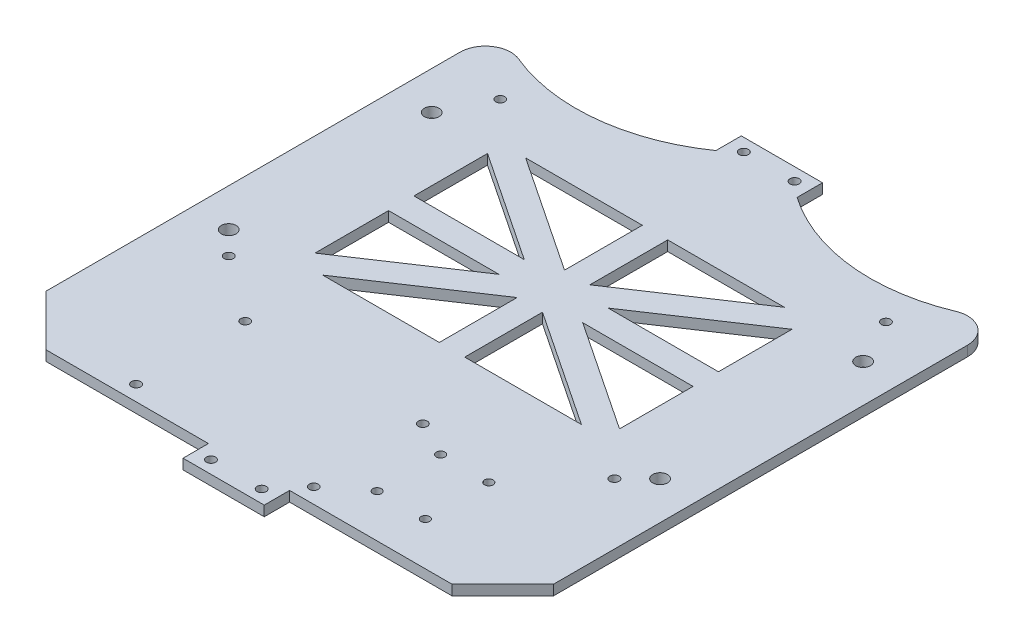
SolidWorks part; units mm, degrees
material "PLA"
ref_plane "Front Plane" through (0, 0, 0) normal (0, 0, 1) x (1, 0, 0)
ref_plane "Top Plane" through (0, 0, 0) normal (0, 1, 0) x (1, 0, 0)
ref_plane "Right Plane" through (0, 0, 0) normal (1, 0, 0) x (0, 0, -1)
sketch "Sketch1" plane through (0, 0, 0) normal (0, 1, 0) x (1, 0, 0)
  line L0 (-100, -229.5) -> (100, -229.5)
  line L1 (100, -229.5) -> (100, -29.5)
  line L2 (100, -29.5) -> (16, -29.5) construction
  line L3 (16, -29.5) -> (16, -19.5)
  line L10 (-16, -29.5) -> (-100, -29.5) construction
  line L11 (-100, -29.5) -> (-100, -229.5)
  line L12 (0, -222) -> (0, 5.5) construction
  line L17 (-10, -24.5) -> (10, -24.5) construction
  line L18 (-16, -29.5) -> (16, -29.5) construction
  line L19 (-10, -234.5) -> (10, -234.5) construction
  line L20 (-16.5139, -104.5) -> (-60, -104.5)
  line L21 (-60, -114.5) -> (-16.5139, -114.5)
  line L22 (-5, -118.8426) -> (-5, -149.5)
  line L27 (5, -118.8426) -> (5, -149.5)
  line L28 (60, -109.5) -> (-60, -109.5) construction
  line L29 (60, -114.5) -> (16.5139, -114.5)
  line L30 (16.5139, -104.5) -> (60, -104.5)
  line L31 (5, -100.1574) -> (5, -69.5)
  line L32 (-5, -100.1574) -> (-5, -69.5)
  line L54 (-60, -69.5) -> (-60, -149.5)
  line L55 (-60, -149.5) -> (60, -149.5)
  line L56 (60, -149.5) -> (60, -69.5)
  line L57 (60, -69.5) -> (-60, -69.5)
  line L59 (-16, -19.5) -> (16, -19.5)
  line L61 (-16, -229.5) -> (-16, -239.5)
  line L62 (-16, -239.5) -> (16, -239.5)
  line L63 (16, -239.5) -> (16, -229.5)
  line L64 (17, -190.5) -> (17, -217.5)
  line L65 (17, -217.5) -> (-18, -217.5)
  line L66 (-18, -217.5) -> (-18, -190.5)
  line L67 (-18, -190.5) -> (17, -190.5)
  line L68 (-50.5, -223.5) -> (-50.5, -180.5) construction
  line L69 (-50.5, -180.5) -> (19.5, -180.5) construction
  line L70 (19.5, -180.5) -> (19.5, -223.5) construction
  line L74 (-60, -75.5093) -> (50.9861, -149.5)
  line L75 (60, -143.4907) -> (-50.9861, -69.5)
  line L76 (-60, -143.4907) -> (50.9861, -69.5)
  line L77 (-50.9861, -149.5) -> (60, -75.5093)
  line L78 (60, -69.5) -> (-60, -149.5) construction
  line L79 (-60, -69.5) -> (60, -149.5) construction
  line L81 (-16, -19.5) -> (-16, -29.5)
  arc A11 (16, -29.5) -> (100, -29.5) centre (58, 30.5) ccw
  arc A12 (-16, -29.5) -> (-100, -29.5) centre (-58, 30.5) cw
  point P5 (-76, -161.5)
  point P6 (-76, -54.5)
  point P7 (76, -161.5)
  point P8 (76, -54.5)
  point P10 (-10, -24.5)
  point P11 (10, -24.5)
  point P12 (0, -229.5)
  point P27 (0, -109.5)
  point P37 (0, -109.5)
  point P53 (0, -239.5)
  point P58 (-50.5, -180.5)
  point P59 (-50.5, -223.5)
  point P60 (19.5, -180.5)
  point P62 (19.5, -223.5)
  point P131 (-85, -72.5)
  point P132 (-85, -152.5)
  point P133 (85, -152.5)
  point P134 (85, -72.5)
  dimension "D29" = 22
  dimension "D30" = 10
  dimension "D31" = 27
  dimension "D39" = 10
  dimension "D12" = 152
  dimension "D13" = 60
  dimension "D4" = 200
  dimension "D8" = 30.5
  dimension "D9" = 200
  dimension "D10" = 10
  dimension "D11" = 16
  dimension "D14" = 107
  dimension "D15" = 25
  dimension "D16" = 20
  dimension "D17" = 5
  dimension "D18" = 20
  dimension "D19" = 40
  dimension "D20" = 10
  dimension "D21" = 10
  dimension "D22" = 19.5
  dimension "D32" = 35
  dimension "D33" = 17
  dimension "D37" = 43
  dimension "D38" = 70
  dimension "D58" = 120
  dimension "D60" = 80
  dimension "D67" = 80
  dimension "D68" = 170
  dimension "D69" = 77
  dimension "D75" = 10
  dimension "D76" = 10
extrude "Boss-Extrude1" add sketch "Sketch1" along normal blind 4 contours L12 | L12 | A12 L11 L0 L1 A11 L3 L57 L56 L55 L54 | L74 L76 L75 L57 L54 | L74 L77 L75 L76 | L77 L74 L55 L56 L75 | L55 L77 L74 L76 L54 | L75 L77 L56 L57 L76 | L62 L63 L0 L61 | L21 L76 L74 L20 L54 | L75 L76 L31 L57 L32 | L77 L75 L29 L56 L30 | L77 L22 L55 L27 L74 | L67 L66 L65 L64 region at (-97.1, 0, 129.5) region at (0, 0, 234.5) region at (-36.3323, 0, 109.5) region at (-31.1426, 0, 88.7382) region at (0, 0, 109.5) region at (-31.1426, 0, 130.2618) region at (31.1426, 0, 130.2618) region at (0, 0, 133.3236) region at (31.1426, 0, 88.7382) region at (0, 0, 85.6764) region at (36.3323, 0, 109.5) region at (-0.5, 0, 204)
hole_wizard "M5 Clearance Hole1" positions "Sketch15" profile "Sketch14" hole size "M5" standard "ISO" end condition through all
sketch "Sketch15" plane through (0, 4, 0) normal (0, 1, 0) x (1, 0, 0)
  point P0 (-85, -72.5)
  point P3 (-85, -152.5)
  point P6 (85, -152.5)
  point P9 (85, -72.5)
sketch "Sketch14" plane through (-85, 4, 72.5) normal (1, 0, 0) x (0, 0, 1)
  line L0 (0, 0) -> (0, 4)
  line L1 (0, 4) -> (2.9, 4)
  line L2 (2.9, 4) -> (2.9, 0)
  line L5 (2.9, 0) -> (0, 0)
  line L11 (0, -6.35) -> (0, 107.95) construction
  dimension "Thru Hole Dia." = 5.8
  dimension "Thru Hole Depth" = 4
fillet "Fillet1" radius 10 2 edges at (100, 2, 29.5) (-100, 2, 29.5)
hole_wizard "M3 Clearance Hole1" positions "Sketch16" profile "Sketch17" hole size "M3" standard "ISO"
sketch "Sketch16" plane through (0, 4, 0) normal (0, 1, 0) x (1, 0, 0)
  point P0 (-50.5, -223.5)
  point P3 (-50.5, -180.5)
  point P6 (19.5, -180.5)
  point P9 (19.5, -223.5)
sketch "Sketch17" plane through (-50.5, 4, 223.5) normal (1, 0, 0) x (0, 0, 1)
  line L0 (0, 0) -> (0, 11.0815)
  line L1 (0, 11.0815) -> (1.8, 10)
  line L2 (1.8, 10) -> (1.8, 0)
  line L5 (1.8, 0) -> (0, 0)
  line L10 (0, 11.0815) -> (-1.8, 10) construction
  line L11 (0, -6.35) -> (0, 107.95) construction
  dimension "Hole Dia." = 3.6
  dimension "Hole Depth" = 10
  dimension "Drill Angle" = 118
chamfer "Chamfer1" distance 20 angle 45 2 edges at (100, 2, 229.5) (-100, 2, 229.5)
hole_wizard "M3 Clearance Hole2" positions "Sketch18" profile "Sketch19" hole size "M3" standard "ISO" end condition through all
sketch "Sketch18" plane through (0, 4, 0) normal (0, 1, 0) x (1, 0, 0)
  point P0 (-76, -54.5)
  point P3 (76, -54.5)
  point P6 (76, -161.5)
  point P9 (-76, -161.5)
  point P12 (-10, -24.5)
  point P15 (10, -24.5)
  point P19 (-10, -234.5)
  point P22 (10, -234.5)
sketch "Sketch19" plane through (-76, 4, 54.5) normal (1, 0, 0) x (0, 0, 1)
  line L0 (0, 0) -> (0, 4)
  line L1 (0, 4) -> (1.8, 4)
  line L2 (1.8, 4) -> (1.8, 0)
  line L5 (1.8, 0) -> (0, 0)
  line L11 (0, -6.35) -> (0, 107.95) construction
  dimension "Thru Hole Dia." = 3.6
  dimension "Thru Hole Depth" = 4
sketch "Sketch20" plane through (0, 4, 0) normal (0, 1, 0) x (1, 0, 0)
  line L0 (16, -229.5) -> (80, -229.5) construction
  line L1 (52.5, -187.5) -> (33.5, -187.5) construction
  line L2 (52.5, -187.5) -> (52.5, -212.5) construction
  line L3 (52.5, -212.5) -> (33.5, -212.5) construction
  line L4 (33.5, -187.5) -> (33.5, -212.5) construction
  line L5 (52.5, -187.5) -> (33.5, -212.5) construction
  line L6 (52.5, -212.5) -> (33.5, -187.5) construction
  circle A0 centre (19.5, -223.5) radius 1.8 construction
  point P0 (43, -200)
  dimension "D1" = 25
  dimension "D2" = 19
  dimension "D3" = 17
  dimension "D4" = 14
hole_wizard "M3 Clearance Hole3" positions "Sketch23" profile "Sketch24" hole size "M3" standard "ISO" end condition through all
sketch "Sketch23" plane through (0, 4, 0) normal (0, 1, 0) x (1, 0, 0)
  point P0 (52.5, -187.5)
  point P3 (33.5, -187.5)
  point P6 (33.5, -212.5)
  point P9 (52.5, -212.5)
sketch "Sketch24" plane through (52.5, 4, 187.5) normal (1, 0, 0) x (0, 0, 1)
  line L0 (0, 0) -> (0, 4)
  line L1 (0, 4) -> (1.7, 4)
  line L2 (1.7, 4) -> (1.7, 0)
  line L5 (1.7, 0) -> (0, 0)
  line L11 (0, -6.35) -> (0, 107.95) construction
  dimension "Thru Hole Dia." = 3.4
  dimension "Thru Hole Depth" = 4
equation "\"w9\"=2"
